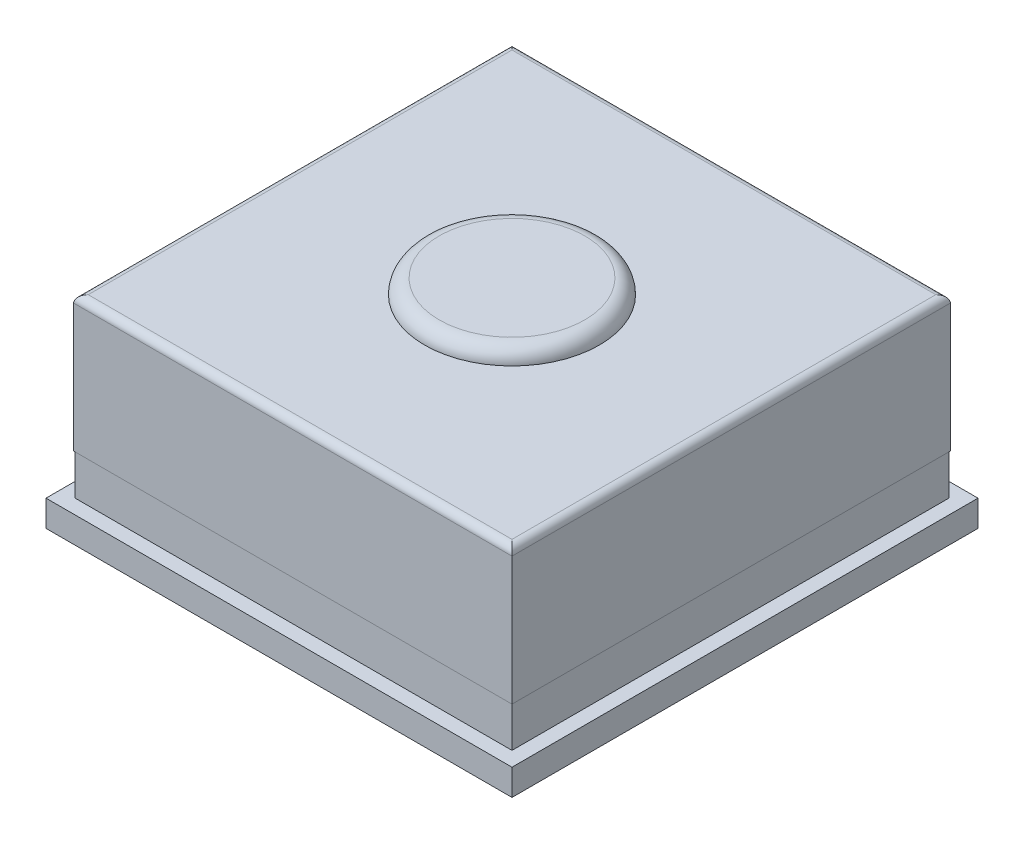
SolidWorks part; units mm, degrees
material "Plastique personnalisé"
ref_plane "Plan de face" through (0, 0, 0) normal (0, 0, 1) x (1, 0, 0)
ref_plane "Plan de dessus" through (0, 0, 0) normal (0, 1, 0) x (1, 0, 0)
ref_plane "Plan de droite" through (0, 0, 0) normal (1, 0, 0) x (0, 0, -1)
sketch "Esquisse1" plane through (0, 0, 0) normal (0, 1, 0) x (1, 0, 0)
  line L1 (-8, -8) -> (8, -8)
  line L2 (-8, -8) -> (-8, 8)
  line L3 (-8, 8) -> (8, 8)
  line L4 (8, -8) -> (8, 8)
  line L5 (-8, -8) -> (8, 8) construction
  line L6 (-8, 8) -> (8, -8) construction
  point P0 (0, 0)
  dimension "D1" = 16
  dimension "D2" = 16
extrude "Boss.-Extru.1" add sketch "Esquisse1" along normal blind 0.9
sketch "Esquisse2" plane through (0, 0, 0) normal (0, 1, 0) x (1, 0, 0)
  line L1 (-7.5, -7.5) -> (7.5, -7.5)
  line L2 (-7.5, -7.5) -> (-7.5, 7.5)
  line L3 (-7.5, 7.5) -> (7.5, 7.5)
  line L4 (7.5, -7.5) -> (7.5, 7.5)
  line L5 (-7.5, -7.5) -> (7.5, 7.5) construction
  line L6 (-7.5, 7.5) -> (7.5, -7.5) construction
  point P1 (0, 0)
  dimension "D1" = 15
  dimension "D2" = 15
extrude "Boss.-Extru.2" add sketch "Esquisse2" along normal blind 2.3
sketch "Esquisse3" plane through (0, 2.3, 0) normal (0, 1, 0) x (1, 0, 0)
  line L1 (-7.525, -7.525) -> (7.525, -7.525)
  line L2 (-7.525, -7.525) -> (-7.525, 7.525)
  line L3 (-7.525, 7.525) -> (7.525, 7.525)
  line L4 (7.525, -7.525) -> (7.525, 7.525)
  line L5 (-7.525, -7.525) -> (7.525, 7.525) construction
  line L6 (-7.525, 7.525) -> (7.525, -7.525) construction
  point P0 (0, 0)
  dimension "D1" = 15.05
  dimension "D2" = 15.05
extrude "Boss.-Extru.3" add sketch "Esquisse3" along normal blind 4.65
sketch "Esquisse4" plane through (0, 6.95, 0) normal (0, 1, 0) x (1, 0, 0)
  circle A0 centre (0, 0) radius 3
extrude "Boss.-Extru.4" add sketch "Esquisse4" along normal blind 0.5
fillet "Congé1" radius 0.5 1 edges at (0, 7.45, 3)
fillet "Congé2" radius 0.25 4 edges at (0, 6.95, 7.525) (7.525, 6.95, 0) (0, 6.95, -7.525) (-7.525, 6.95, 0)
